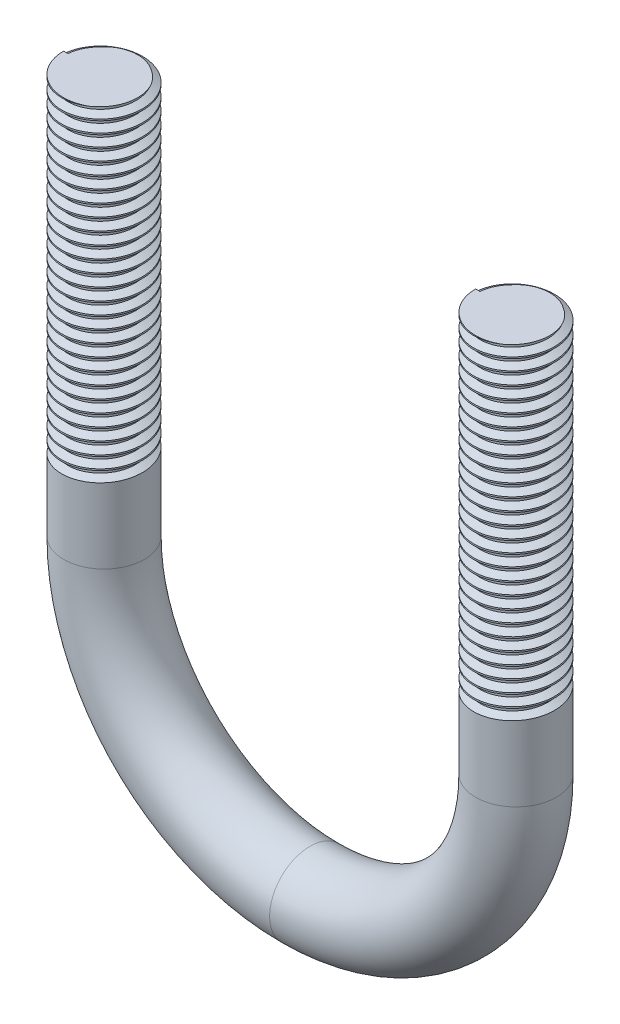
SolidWorks part; units mm, degrees
ref_plane "Front Plane" through (0, 0, 0) normal (0, 0, 1) x (1, 0, 0)
ref_plane "Top Plane" through (0, 0, 0) normal (0, 1, 0) x (1, 0, 0)
ref_plane "Right Plane" through (0, 0, 0) normal (1, 0, 0) x (0, 0, -1)
sketch "Sketch1" plane through (0, 0, 0) normal (0, 0, 1) x (1, 0, 0)
  line L6 (56, -49.5) -> (56, 0)
  line L7 (-5, -49.5) -> (-5, 0)
  arc A2 (25.5, -80) -> (56, -49.5) centre (25.5, -49.5) ccw
  arc A3 (25.5, -80) -> (-5, -49.5) centre (25.5, -49.5) cw
  point P3 (0, -75)
  point P7 (0, 0)
sketch "Sketch2" plane through (0, 0, 0) normal (0, 1, 0) x (1, 0, 0)
  circle A0 centre (0, 0) radius 5
  dimension "D1" = 10
sweep "Sweep1" add profiles "Sketch2" path "Sketch1"
thread "Thread1" pitch 1.5 method cut trim with start face yes trim with end face yes profile "Thread Profile1" start angle 0, offset 1, length 41, pitch 1.5, diameter 10
ref_plane "Plane1" through (-5, 1, 0) normal (0, 0, 1) x (-1, 0, 0)
sketch "Thread Profile1" plane through (-5, 1, 0) normal (0, 0, 1) x (-1, 0, 0)
  line L0 (0, 0) -> (0, 1.5) construction
  line L11 (0, 0) -> (0, 1.3125)
  line L12 (0, 1.3125) -> (-0.8119, 0.8437)
  line L13 (-0.8119, 0.8437) -> (-0.8119, 0.4687)
  line L15 (-0.8119, 0.4687) -> (0, 0)
  line L17 (-0.8119, 0.6562) -> (0, 0.6562) construction
  point P2 (0, 0)
  dimension "Pitch" = 1.5
  dimension "Profile_Angle" = 60
  dimension "Profile_Land" = 0.375
  dimension "Profile_Height" = 0.8119
thread "Thread2" pitch 1.5 method cut profile "Thread Profile2" start angle 0, offset 1, length 41, pitch 1.5, diameter 10
ref_plane "Plane2" through (46, 1, 0) normal (0, 0, 1) x (-1, 0, 0)
sketch "Thread Profile2" plane through (46, 1, 0) normal (0, 0, 1) x (-1, 0, 0)
  line L0 (0, 0) -> (0, 1.5) construction
  line L11 (0, 0) -> (0, 1.3125)
  line L12 (0, 1.3125) -> (-0.8119, 0.8437)
  line L13 (-0.8119, 0.8437) -> (-0.8119, 0.4687)
  line L15 (-0.8119, 0.4687) -> (0, 0)
  line L17 (-0.8119, 0.6562) -> (0, 0.6562) construction
  point P2 (0, 0)
  dimension "Pitch" = 1.5
  dimension "Profile_Angle" = 60
  dimension "Profile_Land" = 0.375
  dimension "Profile_Height" = 0.8119
